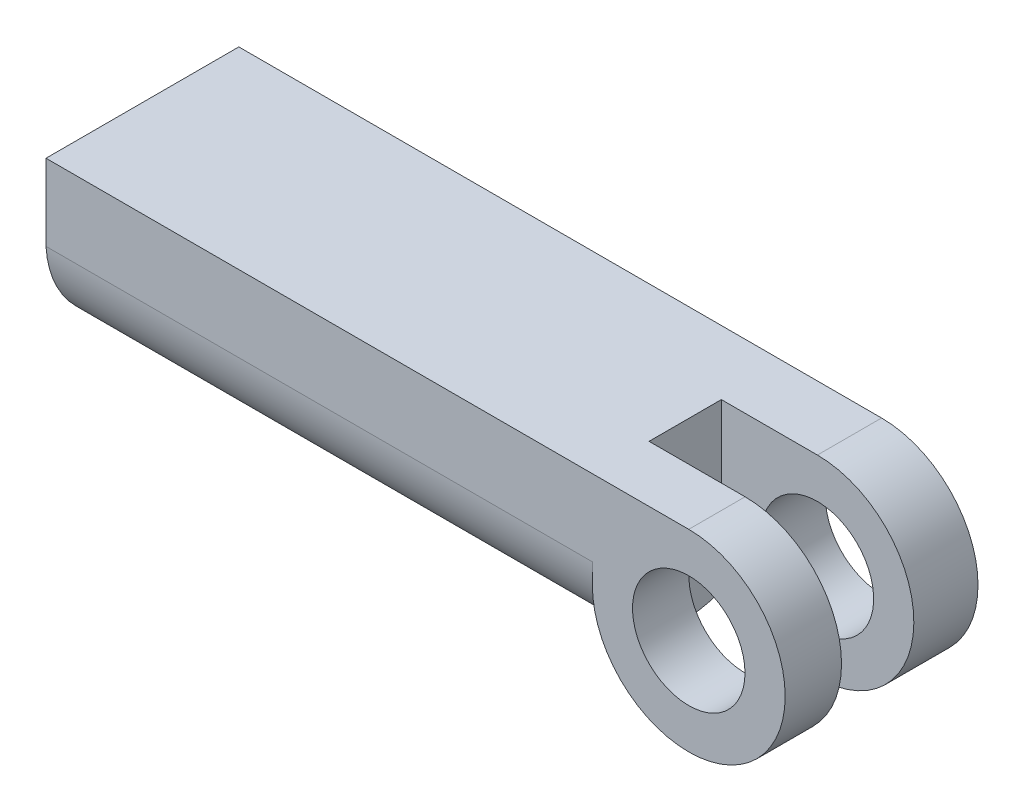
SolidWorks part; units mm, degrees
ref_plane "Front Plane" through (0, 0, 0) normal (0, 0, 1) x (1, 0, 0)
ref_plane "Top Plane" through (0, 0, 0) normal (0, 1, 0) x (1, 0, 0)
ref_plane "Right Plane" through (0, 0, 0) normal (1, 0, 0) x (0, 0, -1)
sketch "Sketch1" plane through (0, 0, 0) normal (0, 0, 1) x (1, 0, 0)
  line L0 (-50.0444, 27.5035) -> (29.9556, 27.5035)
  line L1 (17.9556, 15.5035) -> (17.9556, 6.1362)
  line L2 (17.9556, 6.1362) -> (-39.5444, 6.0035)
  line L3 (-39.5444, 6.0035) -> (-39.5444, 5.0152)
  line L4 (-39.5444, 5.0152) -> (-48.5721, 5.0152)
  line L5 (-48.5721, 5.0152) -> (-48.5721, 6.0035)
  line L6 (-48.5721, 6.0035) -> (-50.0444, 6.0035)
  line L7 (-50.0444, 6.0035) -> (-50.0444, 27.5035)
  arc A0 (29.9556, 27.5035) -> (17.9556, 15.5035) centre (29.9556, 15.5035) cw
  circle A1 centre (29.9556, 15.5035) radius 7
extrude "Boss-Extrude1" add sketch "Sketch1" along normal blind 24
ref_plane "Plane1" through (50, 0, 0) normal (1, 0, 0) x (0, 0, -1)
sketch "Sketch2" plane through (50, 0, 0) normal (1, 0, 0) x (0, 0, -1)
  line L0 (-16.9863, 27.5035) -> (-7.9863, 27.5035)
  line L1 (-24, 27.5035) -> (0, 27.5035) construction
  line L2 (-16.9863, 27.5035) -> (-16.9863, 3.5035)
  line L3 (-24, 3.5035) -> (0, 3.5035) construction
  line L4 (-16.9863, 3.5035) -> (-7.9863, 3.5035)
  line L5 (-7.9863, 3.5035) -> (-7.9863, 27.5035)
  point P5 (-12.4863, 27.5035)
extrude "Cut-Extrude1" cut sketch "Sketch2" against normal blind 32
sketch "Sketch3" plane through (-50.0444, 0, 0) normal (-1, 0, 0) x (0, 0, 1)
  line L3 (0, 27.5035) -> (24, 27.5035)
  line L8 (24, 27.5035) -> (24, 19.5035)
  line L9 (24, 27.5035) -> (24, 6.0035) construction
  line L10 (0, 27.5035) -> (0, 19.5035)
  line L11 (0, 27.5035) -> (0, 6.0035) construction
  line L12 (24, 6.0035) -> (0, 6.0035) construction
  arc A3 (0, 19.5035) -> (12, 6.0035) centre (12.75, 18.7535) ccw
  arc A4 (24, 19.5035) -> (12, 6.0035) centre (11.25, 18.7535) cw
extrude "Cut-Extrude3" cut sketch "Sketch3" against normal blind 68 flip side to cut
sketch "Sketch4" plane through (-50.0444, 0, 0) normal (-1, 0, 0) x (0, 0, 1)
  line L2 (0.1371, 16.7436) -> (23.8629, 16.7436) construction
  arc A0 (0, 18.0035) -> (0.3984, 15.5035) centre (12.75, 18.7535) ccw construction
  arc A1 (23.6016, 15.5035) -> (24, 18.0035) centre (11.25, 18.7535) ccw construction
  circle A2 centre (12, 17.2181) radius 9
  point P0 (12, 17.2181)
  point P15 (12, 16.7436)
extrude "Cut-Extrude4" cut sketch "Sketch4" against normal blind 67
